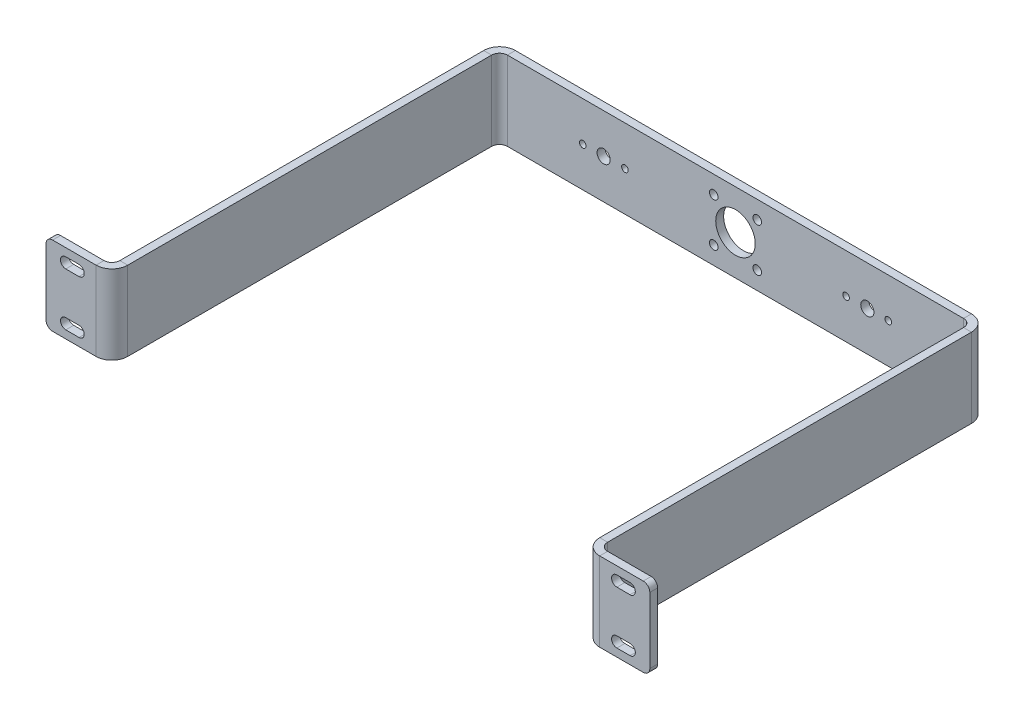
SolidWorks part; units mm, degrees
note: The reader was unsure of these and kept them because the rebuilt part matched: thickness of "Base-Flange1", "Edge-Flange1", "Edge-Flange2", "Edge-Flange3", "Edge-Flange4", "Sheet-Metal1", "Sheet-Metal2", "Sheet-Metal3", "Sheet-Metal4", "Sheet-Metal5", "Sheet-Metal6", "Sheet-Metal8", "Sheet-Metal9"; flange length of "Edge-Flange1", "Edge-Flange2", "Edge-Flange3", "Edge-Flange4".
ref_plane "Front Plane" through (0, 0, 0) normal (0, 0, 1) x (1, 0, 0)
ref_plane "Top Plane" through (0, 0, 0) normal (0, 1, 0) x (1, 0, 0)
ref_plane "Right Plane" through (0, 0, 0) normal (1, 0, 0) x (0, 0, -1)
sketch "Sketch1" plane through (0, 0, 0) normal (0, 0, 1) x (1, 0, 0)
  line L1 (-185, -30) -> (185, -30)
  line L2 (-185, -30) -> (-185, 30)
  line L3 (-185, 30) -> (185, 30)
  line L4 (185, -30) -> (185, 30)
  line L5 (-185, -30) -> (185, 30) construction
  line L6 (-185, 30) -> (185, -30) construction
  point P0 (0, 0)
  dimension "D1" = 60
  dimension "D2" = 370
base flange "Base-Flange1" sketch "Sketch1" thickness 6 reverse thickness direction no parameters "D1"=0.7366
edge flange "Edge-Flange1" sketch "Sketch8" flange angle 90 flange length 300 flange position material inside bend radius 6 thickness 6 relief rectangular parameters "D6"=10
sketch "Sketch8" plane through (185, 0, 0) normal (1, 0, 0) x (0, 1, 0)
  line L2 (-30, 0) -> (-30, 294)
  line L3 (-30, 294) -> (30, 294)
  line L4 (30, 294) -> (30, 0)
  line L7 (-30, 0) -> (30, 0) construction
  line L8 (-30, 0) -> (30, 0)
bend "EdgeBend1" bend radius 6 bend angle 90 parameters "D5"=1
edge flange "Edge-Flange2" sketch "Sketch11" flange angle 90 flange length 300 flange position material inside bend radius 6 thickness 6 relief rectangular parameters "D6"=10
sketch "Sketch11" plane through (-185, 0, 0) normal (-1, 0, 0) x (0, -1, 0)
  line L0 (-30, 0) -> (30, 0) construction
  line L1 (-30, 0) -> (30, 0)
  line L2 (-30, 0) -> (-30, 294)
  line L3 (-30, 294) -> (30, 294)
  line L4 (30, 294) -> (30, 0)
bend "EdgeBend2" bend radius 6 bend angle 90 parameters "D5"=2
edge flange "Edge-Flange3" sketch "Sketch14" flange angle 90 flange length 50 flange position material inside bend radius 6 thickness 6 relief rectangular parameters "D6"=10
sketch "Sketch14" plane through (185, 0, 294) normal (0, 0, 1) x (0, -1, 0)
  line L0 (-30, 0) -> (30, 0) construction
  line L1 (-30, 0) -> (30, 0)
  line L2 (-30, 0) -> (-30, 44)
  line L3 (-30, 44) -> (30, 44)
  line L4 (30, 44) -> (30, 0)
bend "EdgeBend3" bend radius 6 bend angle 90 parameters "D5"=3
edge flange "Edge-Flange4" sketch "Sketch17" flange angle 90 flange length 50 flange position material inside bend radius 6 thickness 6 relief rectangular parameters "D6"=10
sketch "Sketch17" plane through (-185, 0, 294) normal (0, 0, 1) x (0, 1, 0)
  line L2 (-30, 0) -> (-30, 44)
  line L3 (-30, 44) -> (30, 44)
  line L4 (30, 44) -> (30, 0)
  line L7 (-30, 0) -> (30, 0) construction
  line L8 (-30, 0) -> (30, 0)
bend "EdgeBend4" bend radius 6 bend angle 90 parameters "D5"=4
sketch "Sketch18" plane through (0, 0, -6) normal (0, 0, -1) x (-1, 0, 0)
  line L0 (-173, 0) -> (173, 0) construction
  line L2 (0, 30) -> (0, -30) construction
  line L3 (-173, 30) -> (-173, -30) construction
  line L4 (-173, 30) -> (173, 30) construction
  line L5 (173, -30) -> (173, 30) construction
  line L6 (173, -30) -> (-173, -30) construction
  line L12 (105, 0) -> (95, 0) construction
  line L13 (-95, 0) -> (-105, 0) construction
  line L14 (-15, 0) -> (15, 0) construction
  line L15 (0, 0) -> (0, 16.5) construction
  line L16 (0, 16.5) -> (16.5, 16.5) construction
  line L17 (16.5, 16.5) -> (16.5, -16.5) construction
  line L18 (16.5, -16.5) -> (-16.5, -16.5) construction
  line L19 (-16.5, -16.5) -> (-16.5, 16.5) construction
  line L20 (-16.5, 16.5) -> (0, 16.5) construction
  line L21 (0, -16.5) -> (0, 16.5) construction
  line L22 (16.5, 0) -> (-16.5, 0) construction
  circle A7 centre (0, 0) radius 15
  circle A8 centre (-100, 0) radius 5
  circle A9 centre (100, 0) radius 5
  circle A10 centre (-16.5, 16.5) radius 3.25
  circle A11 centre (16.5, 16.5) radius 3.25
  circle A12 centre (16.5, -16.5) radius 3.25
  circle A13 centre (-16.5, -16.5) radius 3.25
  dimension "D5" = 6.5
  dimension "D6" = 6.5
  dimension "D7" = 100
  dimension "D8" = 30
  dimension "D9" = 16.5
  dimension "D10" = 10
  dimension "D11" = 10
  dimension "D4" = 100
  dimension "D2" = 6.5
  dimension "D3" = 6.5
  dimension "D12" = 33
extrude "Cut-Extrude1" cut sketch "Sketch18" against normal blind 65 normal cut yes
sketch "Sketch22" plane through (0, 0, 288) normal (0, 0, -1) x (-1, 0, 0)
  line L2 (0, 59.0261) -> (0, -76.9634) construction
  line L3 (-207.1129, 0) -> (205.8614, 0) construction
  line L4 (-204, 20) -> (-214, 20) construction
  line L5 (-229, -30) -> (-229, 30) construction
  line L6 (-204, 16) -> (-214, 16)
  line L7 (-204, 24) -> (-214, 24)
  line L8 (-229, 30) -> (-191, 30) construction
  line L9 (-204, -20) -> (-214, -20) construction
  line L10 (-204, -16) -> (-214, -16)
  line L11 (-204, -24) -> (-214, -24)
  line L12 (204, 20) -> (214, 20) construction
  line L13 (204, 16) -> (214, 16)
  line L14 (204, 24) -> (214, 24)
  line L15 (204, -20) -> (214, -20) construction
  line L16 (204, -16) -> (214, -16)
  line L17 (204, -24) -> (214, -24)
  arc A4 (-204, 16) -> (-204, 24) centre (-204, 20) ccw
  arc A5 (-214, 24) -> (-214, 16) centre (-214, 20) ccw
  arc A6 (-204, -16) -> (-204, -24) centre (-204, -20) cw
  arc A7 (-214, -24) -> (-214, -16) centre (-214, -20) cw
  arc A8 (204, 16) -> (204, 24) centre (204, 20) cw
  arc A9 (214, 24) -> (214, 16) centre (214, 20) cw
  arc A10 (204, -16) -> (204, -24) centre (204, -20) ccw
  arc A11 (214, -24) -> (214, -16) centre (214, -20) ccw
  point P10 (-209, -20)
  point P20 (209, 20)
  point P21 (-209, 20)
  point P32 (209, -20)
  dimension "D1" = 20
  dimension "D3" = 4
  dimension "D2" = 10
  dimension "D4" = 10
extrude "Cut-Extrude2" cut sketch "Sketch22" against normal blind 65 normal cut yes
sketch "Sketch23" plane through (0, 0, -6) normal (0, 0, -1) x (-1, 0, 0)
  line L1 (83.8752, 5.0062) -> (83.8752, -4.9938) construction
  line L2 (115.8752, 5.0062) -> (115.8752, -4.9938) construction
  line L3 (0, 37.168) -> (0, -35.53) construction
  circle A1 centre (115.8752, 0.0062) radius 2.5
  circle A2 centre (83.8752, 0.0062) radius 2.5
  circle A3 centre (-115.8752, 0.0062) radius 2.5
  circle A4 centre (-83.8752, 0.0062) radius 2.5
  dimension "D1" = 5
  dimension "D2" = 5
extrude "Cut-Extrude3" cut sketch "Sketch23" against normal up to surface (6 mm away) normal cut yes up to face at (13.25, -16.5, 0)
fillet "Fillet1" radius 5 4 edges at (229, -30, 291) (229, 30, 291) (-229, -30, 291) (-229, 30, 291)
sketch "Bend-Lines1" [suppressed] plane through (0, 0, 0) normal (0, 1, 0) x (1, 0, 0)
sketch "Bounding-Box1" [suppressed] plane through (0, 0, 0) normal (0, 1, 0) x (1, 0, 0)
sheet metal parameters "Sheet-Metal1" thickness 6 parameters "D1"=0.7366
flat pattern "Flat-Pattern1" [suppressed]
sketch "Bend-Lines2" plane through (0, 0, 0) normal (0, 1, 0) x (1, 0, 0)
sketch3d "Bounding-Box2" [suppressed]
  line L0 (150, -25, 0) -> (-150, -25, 0) construction
  line L1 (150, 25, 0) -> (-150, 25, 0) construction
  line L2 (150, -25, 0) -> (150, 25, 0) construction
  line L3 (-150, -25, 0) -> (-150, 25, 0) construction
sheet metal parameters "Sheet-Metal2" thickness 6 parameters "D1"=0.7366, "D7"=4
flat pattern "Flat-Pattern1"
sketch "Bend-Lines2" plane through (0, 0, 0) normal (0, 0, 1) x (1, 0, 0)
  line L0 (147.4504, -25) -> (147.4504, 25) construction
  line L1 (147.4504, -25) -> (147.4504, 25) construction
sketch3d "Bounding-Box2" [suppressed]
  line L0 (-150, -25, 0) -> (444.9008, -25, 0) construction
  line L1 (-150, 25, 0) -> (444.9008, 25, 0) construction
  line L2 (-150, -25, 0) -> (-150, 25, 0) construction
  line L3 (444.9008, -25, 0) -> (444.9008, 25, 0) construction
bend of the flat pattern "Flatten-<EdgeBend1>1"
sheet metal parameters "Sheet-Metal3" thickness 6 parameters "D1"=0.7366, "D7"=4
flat pattern "Flat-Pattern1"
sketch "Bend-Lines2" plane through (0, 0, 0) normal (0, 0, 1) x (1, 0, 0)
  line L0 (147.4504, -25) -> (147.4504, 25) construction
  line L1 (147.4504, -25) -> (147.4504, 25) construction
  line L2 (-147.4504, 25) -> (-147.4504, -25) construction
  line L3 (-147.4504, 25) -> (-147.4504, -25) construction
sketch3d "Bounding-Box2" [suppressed]
  line L0 (-444.9008, -25, 0) -> (444.9008, -25, 0) construction
  line L1 (-444.9008, 25, 0) -> (444.9008, 25, 0) construction
  line L2 (-444.9008, -25, 0) -> (-444.9008, 25, 0) construction
  line L3 (444.9008, -25, 0) -> (444.9008, 25, 0) construction
bend of the flat pattern "Flatten-<EdgeBend1>1"
bend of the flat pattern "Flatten-<EdgeBend2>1"
sheet metal parameters "Sheet-Metal4" thickness 6 parameters "D1"=0.7366, "D7"=4
flat pattern "Flat-Pattern1"
sketch "Bend-Lines2" plane through (0, 0, 0) normal (0, 0, 1) x (1, 0, 0)
  line L0 (147.4504, -25) -> (147.4504, 25) construction
  line L1 (147.4504, -25) -> (147.4504, 25) construction
  line L2 (-147.4504, 25) -> (-147.4504, -25) construction
  line L3 (-147.4504, 25) -> (-147.4504, -25) construction
  line L4 (442.3513, -25) -> (442.3513, 25) construction
  line L5 (442.3513, -25) -> (442.3513, 25) construction
sketch3d "Bounding-Box2" [suppressed]
  line L0 (-444.9008, -25, 0) -> (519.8017, -25, 0) construction
  line L1 (-444.9008, 25, 0) -> (519.8017, 25, 0) construction
  line L2 (-444.9008, -25, 0) -> (-444.9008, 25, 0) construction
  line L3 (519.8017, -25, 0) -> (519.8017, 25, 0) construction
bend of the flat pattern "Flatten-<EdgeBend1>1"
bend of the flat pattern "Flatten-<EdgeBend2>1"
bend of the flat pattern "Flatten-<EdgeBend3>1"
sheet metal parameters "Sheet-Metal5" thickness 6 parameters "D1"=0.7366, "D7"=4
flat pattern "Flat-Pattern1"
sketch "Bend-Lines2" plane through (0, 0, 0) normal (0, 0, 1) x (1, 0, 0)
  line L0 (146.7501, -25) -> (146.7501, 25) construction
  line L1 (146.7501, -25) -> (146.7501, 25) construction
  line L2 (-146.7501, 25) -> (-146.7501, -25) construction
  line L3 (-146.7501, 25) -> (-146.7501, -25) construction
  line L4 (440.2503, -25) -> (440.2503, 25) construction
  line L5 (440.2503, -25) -> (440.2503, 25) construction
  line L6 (-440.2503, 25) -> (-440.2503, -25) construction
  line L7 (-440.2503, 25) -> (-440.2503, -25) construction
sketch3d "Bounding-Box2" [suppressed]
  line L0 (-487.0004, -25, 0) -> (487.0004, -25, 0) construction
  line L1 (-487.0004, 25, 0) -> (487.0004, 25, 0) construction
  line L2 (-487.0004, -25, 0) -> (-487.0004, 25, 0) construction
  line L3 (487.0004, -25, 0) -> (487.0004, 25, 0) construction
bend of the flat pattern "Flatten-<EdgeBend1>1"
bend of the flat pattern "Flatten-<EdgeBend2>1"
bend of the flat pattern "Flatten-<EdgeBend3>1"
bend of the flat pattern "Flatten-<EdgeBend4>1"
sheet metal parameters "Sheet-Metal6" thickness 6 parameters "D1"=0.7366, "D7"=4
flat pattern "Flat-Pattern1"
sketch "Bend-Lines2" plane through (0, 0, 0) normal (0, 0, 1) x (1, 0, 0)
  line L0 (146.7501, -25) -> (146.7501, 25) construction
  line L1 (146.7501, -25) -> (146.7501, 25) construction
  line L2 (-146.7501, 25) -> (-146.7501, -25) construction
  line L3 (-146.7501, 25) -> (-146.7501, -25) construction
  line L4 (440.2503, -25) -> (440.2503, 25) construction
  line L5 (440.2503, -25) -> (440.2503, 25) construction
  line L6 (-440.2503, 25) -> (-440.2503, -25) construction
  line L7 (-440.2503, 25) -> (-440.2503, -25) construction
sketch3d "Bounding-Box2" [suppressed]
  line L0 (-487.0004, -25, 0) -> (487.0004, -25, 0) construction
  line L1 (-487.0004, 25, 0) -> (487.0004, 25, 0) construction
  line L2 (-487.0004, -25, 0) -> (-487.0004, 25, 0) construction
  line L3 (487.0004, -25, 0) -> (487.0004, 25, 0) construction
bend of the flat pattern "Flatten-<EdgeBend1>1"
bend of the flat pattern "Flatten-<EdgeBend2>1"
bend of the flat pattern "Flatten-<EdgeBend3>1"
bend of the flat pattern "Flatten-<EdgeBend4>1"
sheet metal parameters "Sheet-Metal8" thickness 6 parameters "D1"=0.7366, "D7"=4
flat pattern "Flat-Pattern1"
sketch "Bend-Lines2" plane through (0, 0, 0) normal (0, 0, 1) x (1, 0, 0)
  line L0 (171.7501, -25) -> (171.7501, 25) construction
  line L1 (171.7501, -25) -> (171.7501, 25) construction
  line L2 (-171.7501, 25) -> (-171.7501, -25) construction
  line L3 (-171.7501, 25) -> (-171.7501, -25) construction
  line L4 (465.2503, -25) -> (465.2503, 25) construction
  line L5 (465.2503, -25) -> (465.2503, 25) construction
  line L6 (-465.2503, 25) -> (-465.2503, -25) construction
  line L7 (-465.2503, 25) -> (-465.2503, -25) construction
sketch3d "Bounding-Box2" [suppressed]
  line L0 (-512.0004, -25, 0) -> (512.0004, -25, 0) construction
  line L1 (-512.0004, 25, 0) -> (512.0004, 25, 0) construction
  line L2 (-512.0004, -25, 0) -> (-512.0004, 25, 0) construction
  line L3 (512.0004, -25, 0) -> (512.0004, 25, 0) construction
bend of the flat pattern "Flatten-<EdgeBend1>1"
bend of the flat pattern "Flatten-<EdgeBend2>1"
bend of the flat pattern "Flatten-<EdgeBend3>1"
bend of the flat pattern "Flatten-<EdgeBend4>1"
sheet metal parameters "Sheet-Metal9" thickness 6 parameters "D1"=0.7366, "D7"=4
flat pattern "Flat-Pattern1"
sketch "Bend-Lines2" plane through (0, 0, 0) normal (0, 0, 1) x (1, 0, 0)
  line L0 (180.0012, -30) -> (180.0012, 30) construction
  line L1 (180.0012, -30) -> (180.0012, 30) construction
  line L2 (-180.0012, 30) -> (-180.0012, -30) construction
  line L3 (-180.0012, 30) -> (-180.0012, -30) construction
  line L4 (470.0036, -30) -> (470.0036, 30) construction
  line L5 (470.0036, -30) -> (470.0036, 30) construction
  line L6 (-470.0036, 30) -> (-470.0036, -30) construction
  line L7 (-470.0036, 30) -> (-470.0036, -30) construction
sketch3d "Bounding-Box2" [suppressed]
  line L0 (-515.0048, 30.0001, 0) -> (515.0048, 30, 0) construction
  line L1 (-515.0048, -29.9999, 0) -> (515.0048, -30, 0) construction
  line L2 (-515.0048, 30.0001, 0) -> (-515.0048, -29.9999, 0) construction
  line L3 (515.0048, 30, 0) -> (515.0048, -30, 0) construction
bend of the flat pattern "Flatten-<EdgeBend1>1"
bend of the flat pattern "Flatten-<EdgeBend2>1"
bend of the flat pattern "Flatten-<EdgeBend3>1"
bend of the flat pattern "Flatten-<EdgeBend4>1"
